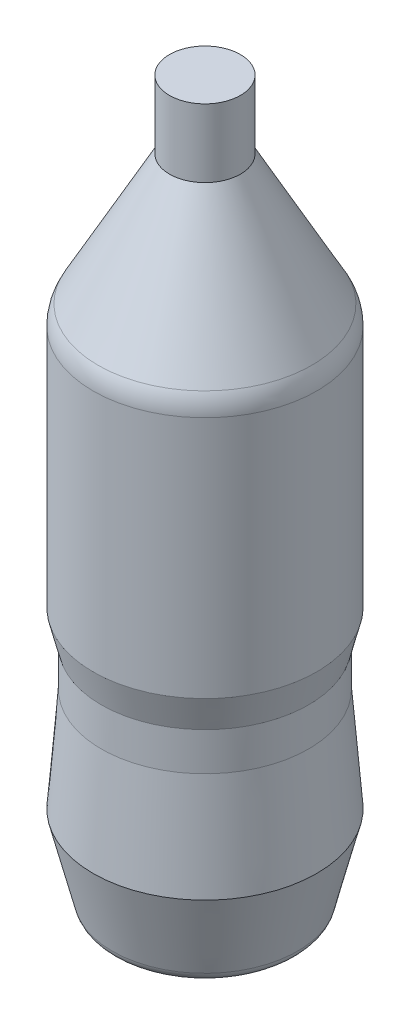
SolidWorks part; units mm, degrees
ref_plane "Front Plane" through (0, 0, 0) normal (0, 0, 1) x (1, 0, 0)
ref_plane "Top Plane" through (0, 0, 0) normal (0, 1, 0) x (1, 0, 0)
ref_plane "Right Plane" through (0, 0, 0) normal (1, 0, 0) x (0, 0, -1)
sketch "Sketch1" plane through (0, 0, 0) normal (0, 1, 0) x (1, 0, 0)
  circle A0 centre (0, 0) radius 41
extrude "Boss-Extrude1" add sketch "Sketch1" along normal blind 265
sketch "Sketch2" plane through (0, 265, 0) normal (0, 1, 0) x (1, 0, 0)
  circle A0 centre (0, 0) radius 13
extrude "Cut-Extrude1" cut sketch "Sketch2" against normal blind 25 flip side to cut
chamfer "Chamfer1" distance 51 distance2 28 1 edges at (0, 240, 41) first distance on face at (0, 0, 41)
sketch "Sketch3" plane through (0, 0, 0) normal (0, -1, 0) x (1, 0, 0)
  circle A0 centre (0, 0) radius 38
extrude "Cut-Extrude2" cut sketch "Sketch3" against normal blind 64 from offset 32 flip side to cut offset against normal yes
chamfer "Chamfer2" distance 38 distance2 3 1 edges at (0, 32, -38) first distance on face at (0, 96, -38)
chamfer "Chamfer3" distance 3 distance2 12 1 edges at (0, 96, -38) first distance on face at (0, 96, -38)
chamfer "Chamfer4" distance 8 distance2 32 1 edges at (0, 0, 41) first distance on face at (0, 0, 41)
fillet "Fillet1" radius 5 1 edges at (0, 0, 33)
fillet "Fillet2" radius 15 1 edges at (0, 189, 41)
